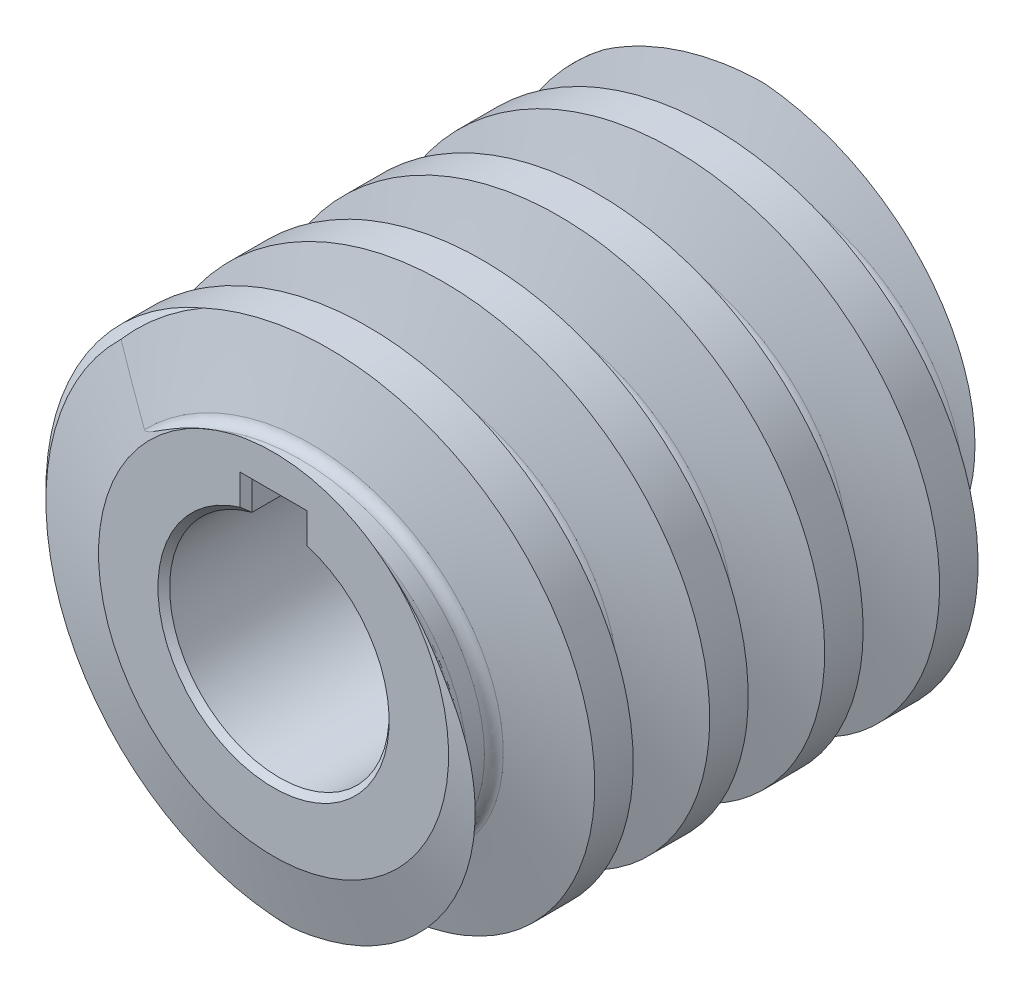
SolidWorks part; units mm, degrees
ref_plane "Front" through (0, 0, 0) normal (0, 0, 1) x (1, 0, 0)
ref_plane "Top" through (0, 0, 0) normal (0, 1, 0) x (1, 0, 0)
ref_plane "Right" through (0, 0, 0) normal (1, 0, 0) x (0, 0, -1)
ref_axis "Axis1" through (0, 0, 55) along (0, 0, -1)
sketch "SketchRevolveWorm01" plane through (0, 0, 0) normal (1, 0, 0) x (0, 0, -1)
  line L0 (0, 0) -> (25.4, 0) construction
  line L1 (22.225, 0) -> (22.225, 19.7536)
  line L2 (22.225, 19.7536) -> (19.7536, 22.225)
  line L3 (19.7536, 22.225) -> (-19.7536, 22.225)
  line L4 (-19.7536, 22.225) -> (-22.225, 19.7536)
  line L5 (-22.225, 19.7536) -> (-22.225, 0)
  line L6 (-22.225, 0) -> (22.225, 0)
  dimension "Side1" = 22.225
  dimension "ChamferX" = 2.4714
  dimension "ChamferY" = 2.4714
  dimension "OutsideDiameter" = 22.225
  dimension "WormLength" = 44.45
revolve "Worm01" add sketch "SketchRevolveWorm01" angle 360 about L0
ref_plane "HelixPlaneWorm01" through (0, 0, 29.9237) normal (0, 0, 1) x (1, 0, 0)
sketch "SketchHelixWorm01" plane through (0, 0, 29.9237) normal (0, 0, 1) x (1, 0, 0)
  circle A0 centre (0, 0) radius 19.05
  dimension "PitchDiameter" = 38.1
curve "GearHelixWorm01" pitch 9.9746 height 59.8473 radius 19.05 centre (0, 0, 29.9237) axis (0, 0, -1) start towards (1, 0, 0)
sketch "SketchToothWorm01" plane through (0, 0, 0) normal (0, 1, 0) x (1, 0, 0)
  line L0 (23.0187, -26.3999) -> (15.9024, -28.247)
  line L1 (15.1892, -29.169) -> (15.1892, -30.6784)
  line L2 (15.9024, -31.6003) -> (23.0187, -33.4474)
  line L3 (23.0187, -33.4474) -> (23.0187, -26.3999)
  arc A0 (15.9024, -28.247) -> (15.1892, -29.169) centre (16.1417, -29.169) ccw
  arc A1 (15.1892, -30.6784) -> (15.9024, -31.6003) centre (16.1417, -30.6784) ccw
sweep "ToothCutWorm01" cut profiles "SketchToothWorm01" path "GearHelixWorm01" align with end faces yes
sketch "BoreRevolveSketch" plane through (0, 0, 0) normal (1, 0, 0) x (0, 0, -1)
  line L0 (0, 0) -> (25.4, 0) construction
  line L1 (-22.225, 0) -> (22.225, 0)
  line L2 (22.225, 0) -> (22.225, 9.525)
  line L3 (22.225, 9.525) -> (-22.225, 9.525)
  line L4 (-22.225, 9.525) -> (-22.225, 0)
  dimension "BoreSide1" = 22.225
  dimension "TaperSide1" = 9.525
  dimension "BoreSide2" = 22.225
  dimension "TaperSide2" = 9.525
revolve "BoreRevolveCut" cut sketch "BoreRevolveSketch" angle 360 about L0
sketch "KeywaySketch" plane through (0, 0, 0) normal (0, 0, 1) x (1, 0, 0)
  line L0 (0, 0) -> (0, 22.225) construction
  line L1 (-2.3812, 9.2225) -> (-2.3813, 11.7348)
  line L2 (-2.3813, 11.7348) -> (2.3813, 11.7348)
  line L3 (2.3813, 11.7348) -> (2.3812, 9.2225)
  line L4 (2.3812, 9.2225) -> (-2.3812, 9.2225)
  circle A0 centre (0, 0) radius 22.225 construction
  circle A1 centre (0, 0) radius 9.525 construction
  point P7 (0, 9.2225)
  point P10 (0, -9.525)
  dimension "D1" = 4.7625
  dimension "D2" = 21.2598
extrude "Keyway" cut sketch "KeywaySketch" against normal through all and the other way through all
sketch "AuxiliarySketchWorm01" plane through (0, 0, 0) normal (0, 0, 1) x (1, 0, 0)
  circle A0 centre (0, 0) radius 19.05 construction
  dimension "PitchDiameter" = 38.1
sketch "Sketch7" plane through (0, 0, 22.225) normal (0, 0, 1) x (1, 0, 0)
  circle A0 centre (0, 0) radius 15.1892
  arc A1 (8.7316, 12.4286) -> (-5.034, 14.3308) centre (0, 0) ccw construction
  circle A2 centre (0, 0) radius 9.525 construction
extrude "Cut-Extrude2" cut sketch "Sketch7" against normal blind 2.54 draft 75 flip side to cut
mirror "Mirror1" about plane through (0, 0, 0) normal (0, 0, 1) of "Cut-Extrude2"
chamfer "Chamfer1" distance 0.508 angle 45 8 edges at (-2.3813, 10.4787, -22.225) (0, 11.7348, -22.225) (2.3812, 10.4787, -22.225) (0, -9.525, -22.225) (2.3813, 10.4787, 22.225) (0, 11.7348, 22.225) (-2.3813, 10.4787, 22.225) (0, -9.525, 22.225)
